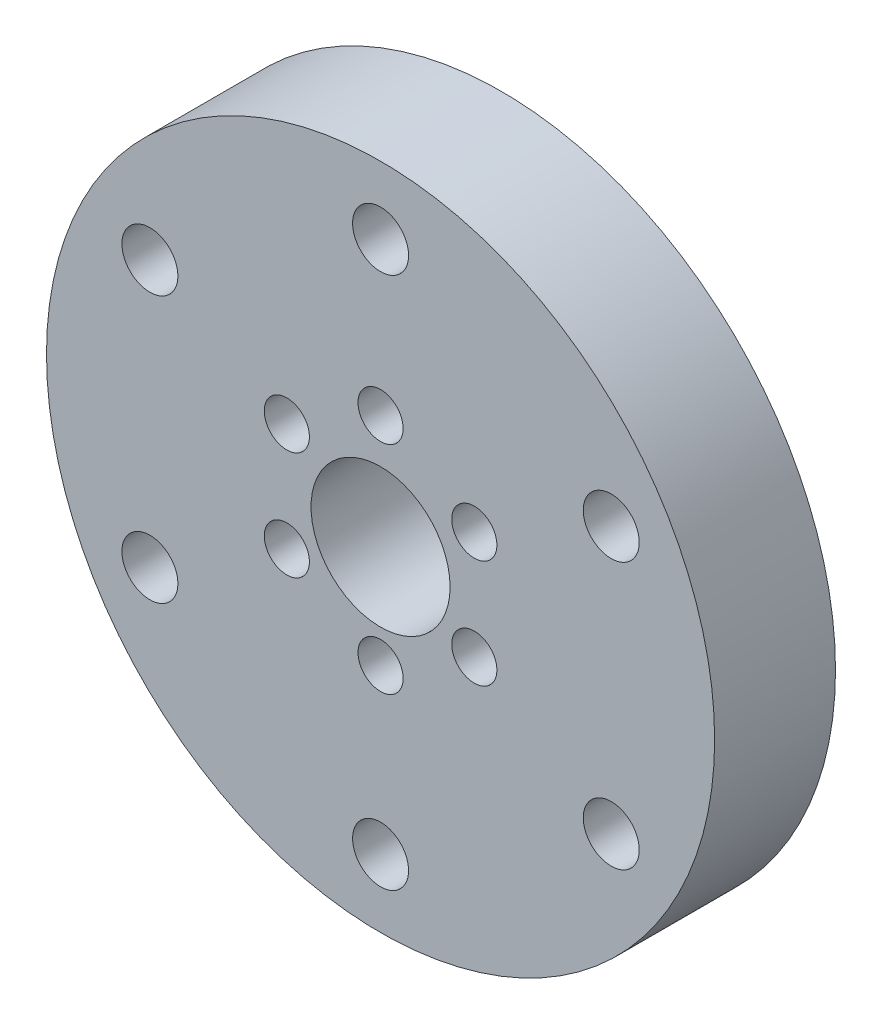
SolidWorks part; units mm, degrees
ref_plane "Front Plane" through (0, 0, 0) normal (0, 0, 1) x (1, 0, 0)
ref_plane "Top Plane" through (0, 0, 0) normal (0, 1, 0) x (1, 0, 0)
ref_plane "Right Plane" through (0, 0, 0) normal (1, 0, 0) x (0, 0, -1)
sketch "Sketch1" plane through (0, 0, 0) normal (0, 0, 1) x (1, 0, 0)
  line L0 (0, -2.035) -> (0, 2.035) construction
  line L1 (0, 0) -> (0, 46.99) construction
  circle A0 centre (0, 0) radius 9.779
  circle A1 centre (0, 0) radius 46.99
  circle A2 centre (0, 16.002) radius 3.175
  circle A3 centre (13.1849, 8.3897) radius 3.175
  circle A4 centre (13.1849, -6.8349) radius 3.175
  circle A5 centre (0, -14.4471) radius 3.175
  circle A6 centre (-13.1849, -6.8349) radius 3.175
  circle A7 centre (-13.1849, 8.3897) radius 3.175
  circle A8 centre (0, 37.465) radius 3.937
  circle A10 centre (32.4456, 18.7325) radius 3.937
  circle A11 centre (32.4456, -18.7325) radius 3.937
  circle A12 centre (0, -37.465) radius 3.937
  circle A13 centre (-32.4456, -18.7325) radius 3.937
  circle A14 centre (-32.4456, 18.7325) radius 3.937
  point P21 (0, 0.7774)
  point P22 (0, 0.7774)
  point P23 (0, 0)
  point P36 (0, 0)
  dimension "D1" = 19.558
  dimension "D2" = 93.98
  dimension "D3" = 6.35
  dimension "D6" = 7.874
  dimension "D4" = 16.002
  dimension "D8" = 37.465
  dimension "D5" = 6
  dimension "D7" = 6
extrude "Boss-Extrude3" add sketch "Sketch1" along normal blind 17
sketch "Sketch2" plane through (0, 0, 17) normal (0, 0, 1) x (1, 0, 0)
  line L0 (0, -9.35) -> (0, 9.35) construction
  circle A0 centre (0, 0) radius 27.94 construction
  circle A1 centre (0, 0) radius 46.99 construction
  spline S0 degree 3 poles (-14.4979, 23.8842) (-5.422, 30.5348) (-13.2477, 46.2899) (0, 46.99) knots 0 0 0 0 1 1 1 1
  spline S1 degree 3 poles (14.4979, 23.8842) (5.422, 30.5348) (13.2477, 46.2899) (0, 46.99) knots 0 0 0 0 1 1 1 1
  point P5 (-16.1177, 22.8224)
  point P6 (-14.4979, 23.8842)
  point P11 (0, 46.99)
  dimension "D1" = 55.88
